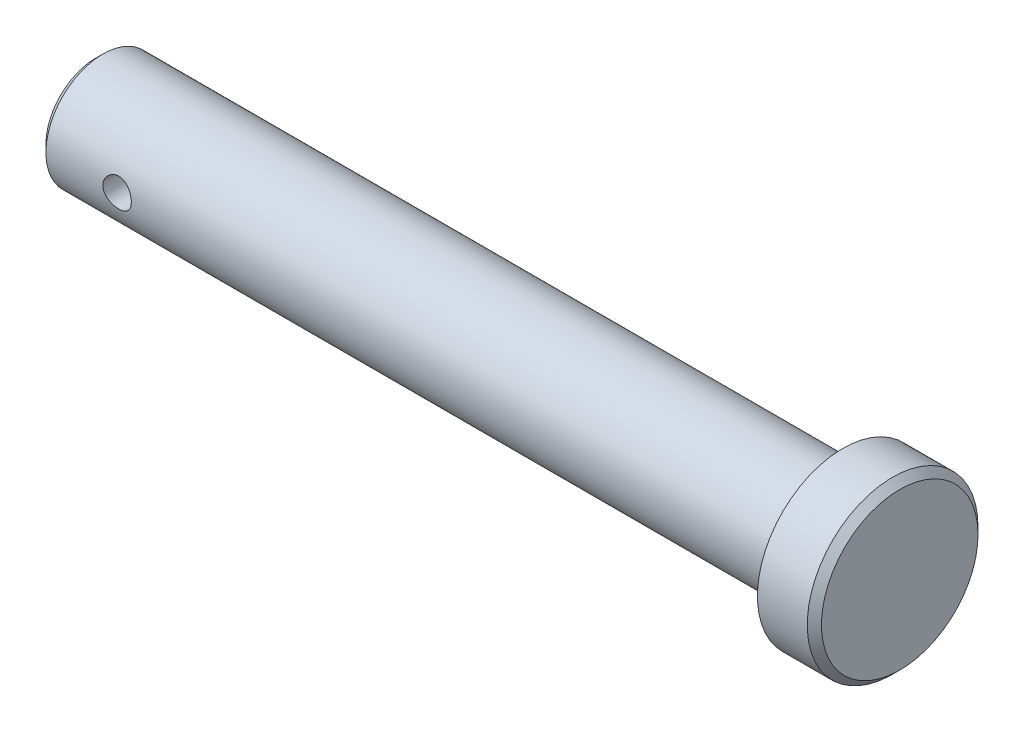
SolidWorks part; units mm, degrees
ref_plane "Front Plane" through (0, 0, 0) normal (0, 0, 1) x (1, 0, 0)
ref_plane "Top Plane" through (0, 0, 0) normal (0, 1, 0) x (1, 0, 0)
ref_plane "Right Plane" through (0, 0, 0) normal (1, 0, 0) x (0, 0, -1)
sketch "Sketch1" plane through (0, 0, 0) normal (1, 0, 0) x (0, 0, -1)
  circle A0 centre (0, 0) radius 8
  circle A1 centre (0, 0) radius 12
  dimension "D1" = 24
  dimension "D2" = 16
extrude "Boss-Extrude1" add sketch "Sketch1" against normal blind 105 contours A0 region at (0, 0, 0)
extrude "Boss-Extrude2" add sketch "Sketch1<4>" along normal blind 8 contours A1 A0 | A0 region at (0, 0, 0) region at (0, 0, 11.6606)
sketch "Sketch1<4>" plane through (0, 0, 0) normal (1, 0, 0) x (0, 0, -1) same geometry as "Sketch1"
chamfer "Chamfer1" distance 1 angle 45 2 edges at (-105, 0, -8) (8, 0, -12)
sketch "Sketch2" plane through (0, 0, 0) normal (0, 0, 1) x (1, 0, 0)
  line L0 (0, 12) -> (0, -12) construction
  line L1 (-104, -8) -> (0, -8) construction
  circle A0 centre (-94, 0) radius 2
  dimension "D1" = 4
  dimension "D2" = 94
  dimension "D3" = 8
extrude "Cut-Extrude1" cut sketch "Sketch2" against normal blind 20 and the other way blind 14
